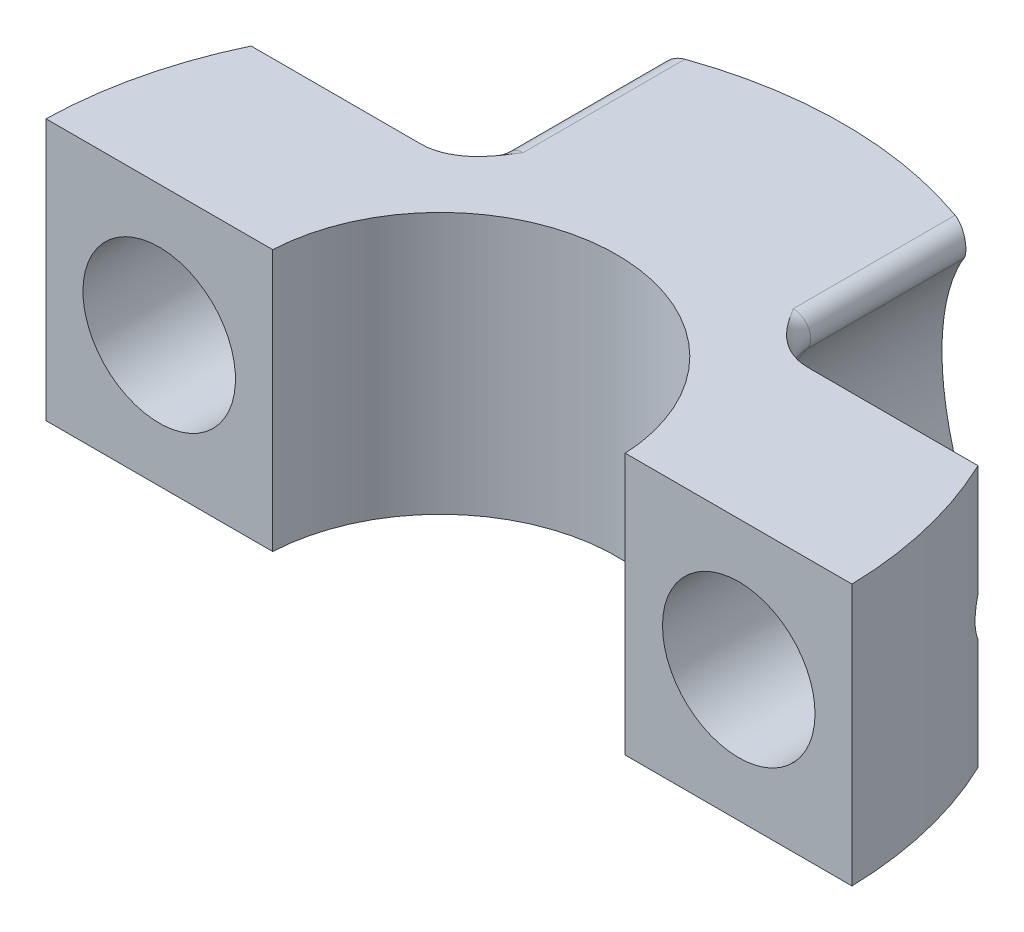
SolidWorks part; units mm, degrees
ref_plane "Front Plane" through (0, 0, 0) normal (0, 0, 1) x (1, 0, 0)
ref_plane "Top Plane" through (0, 0, 0) normal (0, 1, 0) x (1, 0, 0)
ref_plane "Right Plane" through (0, 0, 0) normal (1, 0, 0) x (0, 0, -1)
sketch "Sketch1" plane through (0, 0, 0) normal (0, 1, 0) x (1, 0, 0)
  line L0 (-4.05, 0) -> (-9.25, 0)
  line L1 (4.05, 0) -> (9.25, 0)
  arc A0 (4.05, 0) -> (-4.05, 0) centre (0, 0) ccw
  arc A1 (-9.25, 0) -> (9.25, 0) centre (0, 0) cw
  point P4 (-9.2184, -0.7645)
  point P7 (7.4134, 0)
  dimension "D1" = 4.05
  dimension "D2" = 9.25
extrude "Boss-Extrude1" add sketch "Sketch1" along normal mid plane 6
sketch "Sketch2" plane through (0, 0, 0) normal (0, 0, 1) x (1, 0, 0)
  line L0 (0, 0) -> (0, 3) construction
  line L1 (4.05, 3) -> (-4.05, 3) construction
  line L2 (0, 0) -> (6.65, 0) construction
  circle A0 centre (6.65, 0) radius 1.75
  circle A1 centre (-6.65, 0) radius 1.75
  dimension "D2" = 3.5
  dimension "D1" = 6.65
extrude "Cut-Extrude1" cut sketch "Sketch2" against normal through all both and the other way through all
ref_plane "Plane1" through (0, 0, -10) normal (0, 0, 1) x (1, 0, 0)
sketch "Sketch3" plane through (0, 0, -10) normal (0, 0, 1) x (1, 0, 0)
  line L0 (0, 0) -> (0, 3) construction
  line L1 (9.25, 3) -> (-9.25, 3) construction
  circle A0 centre (6.65, 0) radius 4
  circle A1 centre (-6.65, 0) radius 4
  dimension "D1" = 8
extrude "Cut-Extrude2" cut sketch "Sketch3" along normal blind 6
fillet "Fillet1" radius 0.4 4 edges at (-4.0042, 3, -6.1692) (-4.0042, -3, -6.1692) (4.0042, -3, -6.1692) (4.0042, 3, -6.1692)
fillet "Fillet2" radius 1 6 edges at (-3.4571, -2.7809, -4) (-3.4571, 2.7809, -4) (3.4571, 2.7809, -4) (3.4571, -2.7809, -4) (-2.65, 0, -4) (2.65, 0, -4)
sketch "Sketch4" plane through (0, 3, 0) normal (0, 1, 0) x (1, 0, 0)
  line L1 (9.5, 0.2) -> (-9.5, 0.2)
  line L2 (9.5, 0.2) -> (9.5, -0.2)
  line L3 (9.5, -0.2) -> (-9.5, -0.2)
  line L4 (-9.5, 0.2) -> (-9.5, -0.2)
  line L5 (9.5, 0.2) -> (-9.5, -0.2) construction
  line L6 (9.5, -0.2) -> (-9.5, 0.2) construction
  point P0 (0, 0)
  dimension "D1" = 0.4
  dimension "D2" = 19
extrude "Cut-Extrude3" cut sketch "Sketch4" against normal through all both and the other way through all
